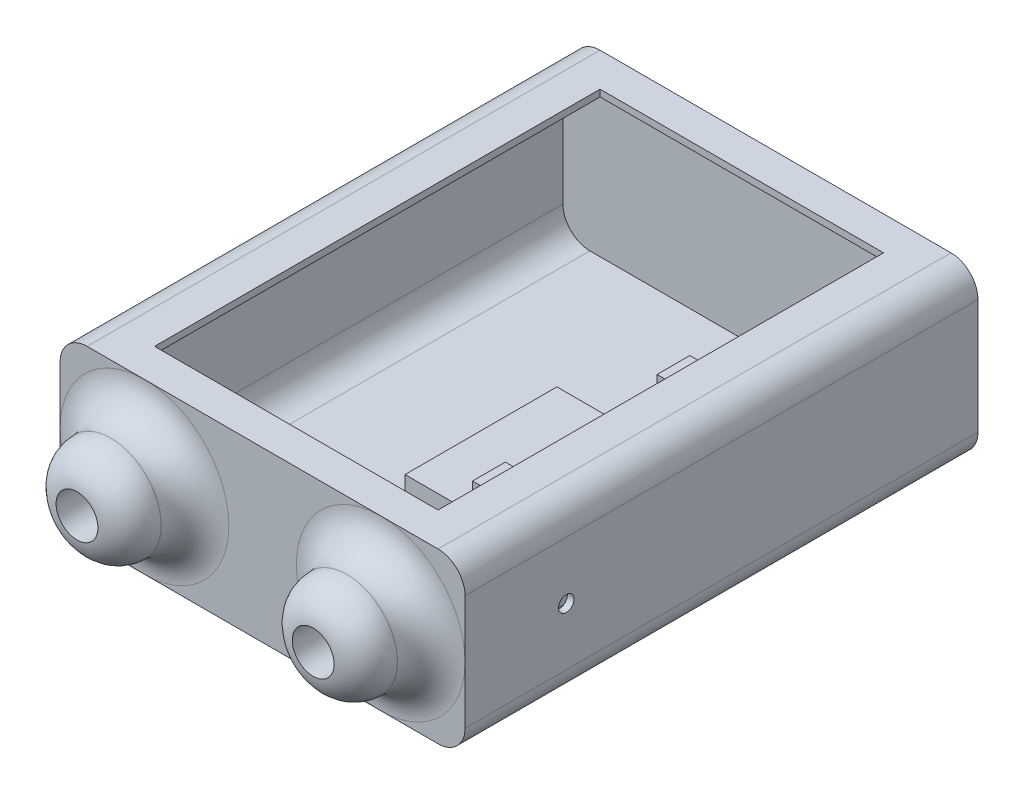
SolidWorks part; units mm, degrees
material "PLA Aero Bambu"
ref_plane "Front Plane" through (0, 0, 0) normal (0, 0, 1) x (1, 0, 0)
ref_plane "Top Plane" through (0, 0, 0) normal (0, 1, 0) x (1, 0, 0)
ref_plane "Right Plane" through (0, 0, 0) normal (1, 0, 0) x (0, 0, -1)
sketch "Sketch1" plane through (0, 0, 0) normal (0, 0, 1) x (1, 0, 0)
  line L1 (-30, 12.5) -> (30, 12.5)
  line L2 (-30, 12.5) -> (-30, -12.5)
  line L3 (-30, -12.5) -> (30, -12.5)
  line L4 (30, 12.5) -> (30, -12.5)
  line L5 (-30, 12.5) -> (30, -12.5) construction
  line L6 (-30, -12.5) -> (30, 12.5) construction
  point P0 (0, 0)
  dimension "D1" = 25
  dimension "D2" = 60
extrude "Boss-Extrude1" add sketch "Sketch1" against normal blind 1
sketch "Sketch2" plane through (0, 0, -1) normal (0, 0, -1) x (-1, 0, 0)
  line L0 (-30, 12.5) -> (-30, -12.5)
  line L1 (30, -12.5) -> (-30, -12.5) construction
  line L2 (-30, -12.5) -> (30, -12.5)
  line L3 (30, -12.5) -> (30, 12.5)
  line L4 (30, 12.5) -> (-30, 12.5)
  line L5 (29, 11.5) -> (-29, 11.5)
  line L6 (-29, 11.5) -> (-29, -11.5)
  line L7 (-29, -11.5) -> (29, -11.5)
  line L8 (29, -11.5) -> (29, 11.5)
  dimension "D1" = 1
extrude "Boss-Extrude2" add sketch "Sketch2" along normal blind 75
fillet "Fillet2" radius 4 8 edges at (30, 12.5, -38) (30, -12.5, -38) (-30, -12.5, -38) (-30, 12.5, -38) (-29, -11.5, -38.5) (-29, 11.5, -38.5) (29, 11.5, -38.5) (29, -11.5, -38.5)
sketch "Sketch4" plane through (0, 0, 0) normal (0, 0, 1) x (1, 0, 0)
  line L0 (-17.5, 0) -> (17.5, 0) construction
  circle A0 centre (-17.5, 0) radius 7.5
  circle A1 centre (-17.5, 0) radius 3.1
  circle A2 centre (17.5, 0) radius 3.1
  circle A3 centre (17.5, 0) radius 7.5
  point P5 (0, 0)
  dimension "D1" = 6.2
  dimension "D2" = 15
  dimension "D3" = 35
extrude "Boss-Extrude3" add sketch "Sketch4" along normal blind 10
fillet "Fillet3" radius 5 4 edges at (-10, 0, 0) (-10, 0, 10) (25, 0, 10) (25, 0, 0)
sketch "Sketch18" plane through (0, 0, 0) normal (0, 0, 1) x (1, 0, 0)
  circle A0 centre (-17.5, 0) radius 2
  circle A1 centre (17.5, 0) radius 2
  dimension "D1" = 4
extrude "Cut-Extrude6" cut sketch "Sketch18" against normal up to surface (1 mm away) up to face at (0, 0, -1)
sketch "Sketch5" plane through (30, 0, 0) normal (1, 0, 0) x (0, 0, -1)
  circle A0 centre (15, 0) radius 1.15
  dimension "D1" = 2.3
  dimension "D2" = 15
extrude "Cut-Extrude1" cut sketch "Sketch5" against normal through all contours A0
sketch "Sketch10" plane through (0, -11.5, 0) normal (0, 1, 0) x (1, 0, 0)
  line L0 (17.5, 0) -> (-17.5, 0) construction
  line L4 (26, 0) -> (26, 76) construction
  line L6 (-3.9968, 47.6018) -> (18.48, 47.6018)
  line L7 (-3.9968, 47.6018) -> (-3.9968, 25.1)
  line L8 (-3.9968, 25.1) -> (18.48, 25.1)
  line L9 (18.48, 47.6018) -> (18.48, 25.1)
  dimension "D1" = 25.1
  dimension "D2" = 7.52
  dimension "D3" = 22.5018
  dimension "D4" = 22.4768
extrude "Boss-Extrude4" add sketch "Sketch10" along normal blind 6
sketch "Sketch12" plane through (0, -11.5, 0) normal (0, 1, 0) x (1, 0, 0)
  line L5 (25, 1) -> (25, 76) construction
  line L10 (10.83, 25.1335) -> (13.33, 25.1335)
  line L12 (10.83, 25.1335) -> (10.83, 20.275)
  line L13 (10.83, 20.275) -> (13.33, 20.275)
  line L14 (13.33, 25.1335) -> (13.33, 20.275)
  line L15 (10.83, 47.6165) -> (13.33, 47.6165)
  line L16 (10.83, 47.6165) -> (10.83, 52.475)
  line L17 (10.83, 52.475) -> (13.33, 52.475)
  line L18 (13.33, 47.6165) -> (13.33, 52.475)
  dimension "D1" = 4.8585
  dimension "D4" = 2.5
  dimension "D5" = 11.67
  dimension "D6" = 22.483
  dimension "D7" = 20.275
extrude "Boss-Extrude5" add sketch "Sketch12" along normal blind 15
sketch "Sketch13" plane through (13.33, 0, 0) normal (1, 0, 0) x (0, 0, -1)
  circle A0 centre (22.7042, 0) radius 1.35
  circle A1 centre (50.0458, 0) radius 1.35
  dimension "D2" = 2.7
  dimension "D3" = 2.7
  dimension "D4" = 27.3415
  dimension "D1" = 22.7042
extrude "Cut-Extrude3" cut sketch "Sketch13" against normal blind 12
sketch "Sketch15" plane through (0, -11.5, 0) normal (0, 1, 0) x (1, 0, 0)
  line L0 (29, 76) -> (29, 1) construction
  line L1 (14, 18) -> (19, 18)
  line L2 (14, 18) -> (14, 12)
  line L3 (14, 12) -> (19, 12)
  line L4 (19, 18) -> (19, 12)
  line L5 (14, 12) -> (19, 18) construction
  line L6 (19, 12) -> (14, 18) construction
  line L8 (25, 1) -> (-25, 1) construction
  point P6 (16.5, 15)
  dimension "D1" = 10
  dimension "D2" = 6
  dimension "D3" = 5
  dimension "D4" = 14
extrude "Boss-Extrude6" add sketch "Sketch15" along normal blind 14
sketch "Sketch16" plane through (19, 0, 0) normal (1, 0, 0) x (0, 0, -1)
  circle A0 centre (15, 0) radius 1.25
extrude "Cut-Extrude4" cut sketch "Sketch16" against normal blind 5
sketch "Sketch19" plane through (0, 12.5, 0) normal (0, 1, 0) x (1, 0, 0)
  line L0 (-26, 76) -> (-26, 0) construction
  line L1 (-21, 5) -> (21, 5)
  line L2 (-21, 5) -> (-21, 71)
  line L3 (-21, 71) -> (21, 71)
  line L4 (21, 5) -> (21, 71)
  line L5 (17.5, 0) -> (-17.5, 0) construction
  line L6 (-26, 76) -> (26, 76) construction
  point P6 (0, 5)
  dimension "D1" = 5
  dimension "D2" = 5
  dimension "D3" = 5
extrude "Cut-Extrude7" cut sketch "Sketch19" against normal up to surface (1 mm away) up to face at (0, 11.5, -38.5)
sketch "Sketch17" [suppressed] plane through (0, 0, -76) normal (0, 0, -1) x (-1, 0, 0)
  line L0 (20, 8.5) -> (-20, 8.5)
split "Split1" [suppressed] bodies to split 114
sketch "Sketch20" plane through (0, 0, -76) normal (0, 0, -1) x (-1, 0, 0)
  line L0 (-25, 11.5) -> (25, 11.5)
  line L1 (29, 7.5) -> (29, -7.5)
  line L2 (-25, -11.5) -> (25, -11.5)
  line L3 (-29, 7.5) -> (-29, -7.5)
  arc A0 (-29, 7.5) -> (-25, 11.5) centre (-25, 7.5) cw
  arc A1 (25, 11.5) -> (29, 7.5) centre (25, 7.5) cw
  arc A2 (25, -11.5) -> (29, -7.5) centre (25, -7.5) ccw construction
  arc A3 (25, -11.5) -> (29, -7.5) centre (25, -7.5) ccw construction
  arc A4 (29, -7.5) -> (25, -11.5) centre (25, -7.5) cw
  arc A5 (-25, -11.5) -> (-29, -7.5) centre (-25, -7.5) cw
extrude "Boss-Extrude7" add sketch "Sketch20" against normal blind 2.5
